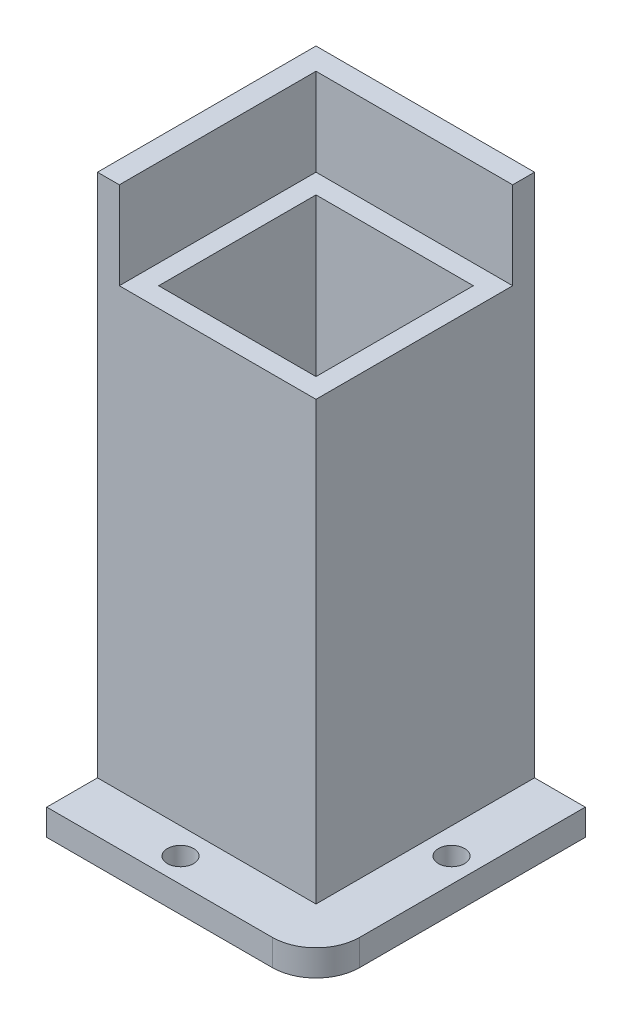
SolidWorks part; units mm, degrees
ref_plane "Front Plane" through (0, 0, 0) normal (0, 0, 1) x (1, 0, 0)
ref_plane "Top Plane" through (0, 0, 0) normal (0, 1, 0) x (1, 0, 0)
ref_plane "Right Plane" through (0, 0, 0) normal (1, 0, 0) x (0, 0, -1)
sketch "Sketch1" plane through (0, 0, 0) normal (0, 1, 0) x (1, 0, 0)
  line L1 (-12.5, 12.5) -> (12.5, 12.5)
  line L2 (-12.5, 12.5) -> (-12.5, -12.5)
  line L3 (-12.5, -12.5) -> (12.5, -12.5)
  line L4 (12.5, 12.5) -> (12.5, -12.5)
  line L5 (-12.5, 12.5) -> (12.5, -12.5) construction
  line L6 (-12.5, -12.5) -> (12.5, 12.5) construction
  point P0 (0, 0)
  dimension "D1" = 25
  dimension "D2" = 25
extrude "Boss-Extrude1" add sketch "Sketch1" along normal blind 63
sketch "Sketch2" plane through (0, 63, 0) normal (0, 1, 0) x (1, 0, 0)
  line L1 (12.5, -12.5) -> (-10, -12.5)
  line L2 (12.5, -12.5) -> (12.5, 10)
  line L3 (12.5, 10) -> (-10, 10)
  line L4 (-10, -12.5) -> (-10, 10)
  dimension "D1" = 22.5
  dimension "D2" = 22.5
extrude "Cut-Extrude2" cut sketch "Sketch2" against normal blind 10
sketch "Sketch4" plane through (0, 0, 0) normal (0, -1, 0) x (1, 0, 0)
  line L1 (-12.5, -12.5) -> (18.3, -12.5)
  line L2 (-12.5, -12.5) -> (-12.5, 18.3)
  line L3 (-12.5, 18.3) -> (13.3, 18.3)
  line L4 (18.3, -12.5) -> (18.3, 13.3)
  line L5 (12.5, 12.5) -> (-12.5, 12.5)
  line L6 (12.5, 12.5) -> (12.5, -12.5)
  line L7 (12.5, -12.5) -> (-12.5, -12.5)
  line L8 (-12.5, 12.5) -> (-12.5, -12.5)
  arc A0 (13.3, 18.3) -> (18.3, 13.3) centre (13.3, 13.3) cw
  circle A1 centre (0, 15.5) radius 1.5
  circle A2 centre (15.5, 0) radius 1.5
  point P11 (18.3, 18.3)
  line M9 (12.5, -12.5) -> (12.5, 12.5)
  line M10 (12.5, 12.5) -> (-12.5, 12.5)
  dimension "D3" = 5
  dimension "D4" = 3
  dimension "D5" = 3
  dimension "D1" = 30.8
  dimension "D2" = 30.8
  dimension "D6" = 12.5
  dimension "D7" = 12.5
  dimension "D8" = 28
  dimension "D9" = 28
extrude "Boss-Extrude2" add sketch "Sketch4" against normal blind 3 contours L1 L4 L3 L2 M10 M9 region at (12.9356, 0, 0)
sketch "Sketch5" plane through (0, 53, 0) normal (0, 1, 0) x (1, 0, 0)
  line L0 (-10, -1.25) -> (12.5, -1.25) construction
  line L1 (-10, 10) -> (-10, -12.5) construction
  line L2 (12.5, -12.5) -> (12.5, 10) construction
  line L4 (-7.75, 7.75) -> (10.25, 7.75)
  line L5 (-7.75, 7.75) -> (-7.75, -10.25)
  line L6 (-7.75, -10.25) -> (10.25, -10.25)
  line L7 (10.25, 7.75) -> (10.25, -10.25)
  line L8 (-7.75, 7.75) -> (10.25, -10.25) construction
  line L9 (-7.75, -10.25) -> (10.25, 7.75) construction
  point P6 (1.25, -1.25)
  dimension "D1" = 18
  dimension "D2" = 18
extrude "Cut-Extrude3" cut sketch "Sketch5" against normal blind 50
